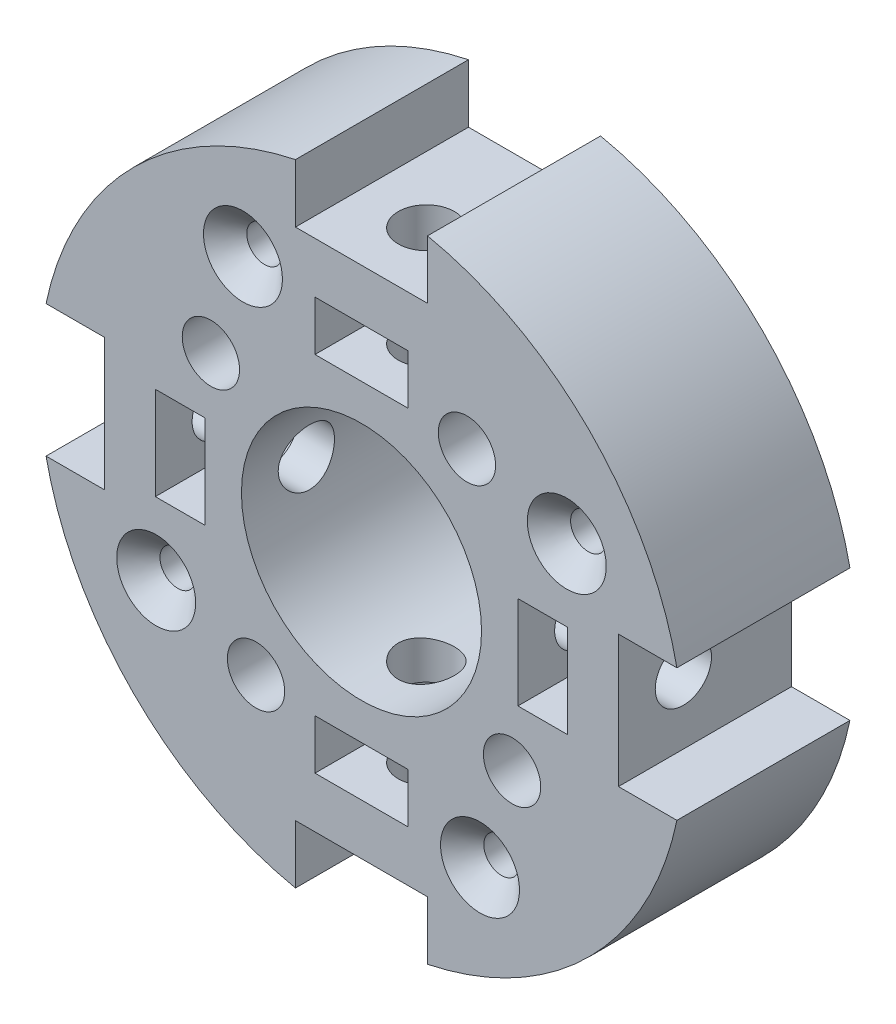
SolidWorks part; units mm, degrees
ref_plane "Plan de face" through (0, 0, 0) normal (0, 0, 1) x (1, 0, 0)
ref_plane "Plan de dessus" through (0, 0, 0) normal (0, 1, 0) x (1, 0, 0)
ref_plane "Plan de droite" through (0, 0, 0) normal (1, 0, 0) x (0, 0, -1)
sketch "Esquisse1" plane through (0, 0, 0) normal (0, 0, 1) x (1, 0, 0)
  line L1 (-29.4129, -5.9059) -> (-23.9629, -5.9059) construction
  line L3 (-29.4129, 5.9059) -> (-23.9629, 5.9059) construction
  line L4 (-23.9629, -5.9059) -> (-23.9629, 5.9059) construction
  line L5 (-29.4129, -5.9059) -> (-23.9629, 5.9059) construction
  line L6 (-29.4129, 5.9059) -> (-23.9629, -5.9059) construction
  line L7 (-5.9059, 29.4129) -> (-5.9059, 23.9629) construction
  line L8 (-5.9059, 23.9629) -> (5.9059, 23.9629) construction
  line L9 (5.9059, 29.4129) -> (5.9059, 23.9629) construction
  line L11 (29.4129, 5.9059) -> (23.9629, 5.9059) construction
  line L12 (23.9629, 5.9059) -> (23.9629, -5.9059) construction
  line L13 (29.4129, -5.9059) -> (23.9629, -5.9059) construction
  line L15 (5.9059, -29.4129) -> (5.9059, -23.9629) construction
  line L16 (5.9059, -23.9629) -> (-5.9059, -23.9629) construction
  line L17 (-5.9059, -29.4129) -> (-5.9059, -23.9629) construction
  line L18 (-6.1059, 29.1677) -> (-6.1059, 23.7629)
  line L19 (-6.1059, 23.7629) -> (6.1059, 23.7629)
  line L20 (6.1059, 29.1677) -> (6.1059, 23.7629)
  line L21 (29.1677, 6.1059) -> (23.7629, 6.1059)
  line L22 (23.7629, 6.1059) -> (23.7629, -6.1059)
  line L23 (29.1677, -6.1059) -> (23.7629, -6.1059)
  line L24 (6.1059, -29.1677) -> (6.1059, -23.7629)
  line L25 (6.1059, -23.7629) -> (-6.1059, -23.7629)
  line L26 (-6.1059, -29.1677) -> (-6.1059, -23.7629)
  line L27 (-29.1677, -6.1059) -> (-23.7629, -6.1059)
  line L28 (-23.7629, -6.1059) -> (-23.7629, 6.1059)
  line L29 (-29.1677, 6.1059) -> (-23.7629, 6.1059)
  line L30 (-4.3, 19.0629) -> (4.3, 19.0629)
  line L31 (-4, 18.7629) -> (4, 18.7629) construction
  line L32 (-4, 18.7629) -> (-4, 14.7629) construction
  line L33 (-4, 14.7629) -> (4, 14.7629) construction
  line L34 (4, 18.7629) -> (4, 14.7629) construction
  line L35 (-4, 18.7629) -> (4, 14.7629) construction
  line L36 (-4, 14.7629) -> (4, 18.7629) construction
  line L37 (4.3, 19.0629) -> (4.3, 14.4629)
  line L38 (-4.3, 14.4629) -> (4.3, 14.4629)
  line L39 (-4.3, 19.0629) -> (-4.3, 14.4629)
  line L40 (19.0629, 4.3) -> (19.0629, -4.3)
  line L41 (19.0629, -4.3) -> (14.4629, -4.3)
  line L42 (14.4629, 4.3) -> (14.4629, -4.3)
  line L43 (19.0629, 4.3) -> (14.4629, 4.3)
  line L44 (4.3, -19.0629) -> (-4.3, -19.0629)
  line L45 (-4.3, -19.0629) -> (-4.3, -14.4629)
  line L46 (4.3, -14.4629) -> (-4.3, -14.4629)
  line L47 (4.3, -19.0629) -> (4.3, -14.4629)
  line L48 (-19.0629, -4.3) -> (-19.0629, 4.3)
  line L49 (-19.0629, 4.3) -> (-14.4629, 4.3)
  line L50 (-14.4629, -4.3) -> (-14.4629, 4.3)
  line L51 (-19.0629, -4.3) -> (-14.4629, -4.3)
  line L52 (-0.2119, 0.3671) -> (-25000.2119, 43301.6373) construction
  line L53 (0, 0) -> (-40957.6022, 28678.8218) construction
  line L54 (0, -1000) -> (0, 49000) construction
  arc A0 (-29.4129, -5.9059) -> (-5.9059, -29.4129) centre (0, 0) ccw construction
  circle A1 centre (0, 0) radius 11.1
  circle A2 centre (-10.9602, 18.9835) radius 1.65
  circle A3 centre (18.9835, 10.9602) radius 1.65
  circle A4 centre (10.9602, -18.9835) radius 1.65
  circle A5 centre (-18.9835, -10.9602) radius 1.65
  arc A6 (5.9059, -29.4129) -> (29.4129, -5.9059) centre (0, 0) ccw construction
  arc A7 (29.4129, 5.9059) -> (5.9059, 29.4129) centre (0, 0) ccw construction
  arc A8 (-5.9059, 29.4129) -> (-29.4129, 5.9059) centre (0, 0) ccw construction
  arc A9 (29.1677, 6.1059) -> (6.1059, 29.1677) centre (0, 0) ccw
  arc A10 (6.1059, -29.1677) -> (29.1677, -6.1059) centre (0, 0) ccw
  arc A11 (-29.1677, -6.1059) -> (-6.1059, -29.1677) centre (0, 0) ccw
  arc A12 (-6.1059, 29.1677) -> (-29.1677, 6.1059) centre (0, 0) ccw
  circle A13 centre (-13.9256, 9.7508) radius 2.65
  circle A14 centre (9.7508, 13.9256) radius 2.65
  circle A15 centre (13.9256, -9.7508) radius 2.65
  circle A16 centre (-9.7508, -13.9256) radius 2.65
  point P4 (-26.6879, 0)
  point P22 (0, 0)
  point P33 (0, 0)
  point P51 (0, 16.7629)
  point P56 (0, 23.7629)
  point P75 (0, 0)
  point P90 (0, 0)
  dimension "D1" = 60
  dimension "D2" = 22.2
  dimension "D7" = 3.3
  dimension "D14" = 5.3
  dimension "D18" = 4
  dimension "D3" = 5.45
  dimension "D4" = 4
  dimension "D5" = 21.9203
  dimension "D6" = 0.2
  dimension "D9" = 8
  dimension "D10" = 4
  dimension "D11" = 5
  dimension "D15" = 17
  dimension "D16" = 30
  dimension "D17" = 55
  dimension "D12" = 0.3
  dimension "D8" = 4
  dimension "D13" = 4
extrude "Boss.-Extru.1" add sketch "Esquisse1" along normal blind 16 contours A0 A1 A2 A3 | A0 A1 A5 A4 | A0 | A0 region at (-6.9309, 26.4653, 0)
sketch "Esquisse5" plane through (0, 0, 0) normal (0, 0, -1) x (-1, 0, 0)
  line L0 (9.1913, 9.7508) -> (11.5584, 5.6508)
  line L1 (-9.7508, 9.1913) -> (-5.6508, 11.5584)
  line L2 (-5.6508, 11.5584) -> (-5.6508, 16.2927)
  line L3 (-5.6508, 16.2927) -> (-9.7508, 18.6599)
  line L4 (-9.7508, 18.6599) -> (-13.8508, 16.2927)
  line L5 (-13.8508, 16.2927) -> (-13.8508, 11.5584)
  line L6 (-13.8508, 11.5584) -> (-9.7508, 9.1913)
  line L7 (11.5584, 5.6508) -> (16.2927, 5.6508)
  line L8 (16.2927, 5.6508) -> (18.6599, 9.7508)
  line L9 (18.6599, 9.7508) -> (16.2927, 13.8508)
  line L10 (16.2927, 13.8508) -> (11.5584, 13.8508)
  line L11 (11.5584, 13.8508) -> (9.1913, 9.7508)
  line L12 (9.7508, -9.1913) -> (5.6508, -11.5584)
  line L13 (5.6508, -11.5584) -> (5.6508, -16.2927)
  line L14 (5.6508, -16.2927) -> (9.7508, -18.6599)
  line L15 (9.7508, -18.6599) -> (13.8508, -16.2927)
  line L16 (13.8508, -16.2927) -> (13.8508, -11.5584)
  line L17 (13.8508, -11.5584) -> (9.7508, -9.1913)
  line L18 (-9.1913, -9.7508) -> (-11.5584, -5.6508)
  line L19 (-11.5584, -5.6508) -> (-16.2927, -5.6508)
  line L20 (-16.2927, -5.6508) -> (-18.6599, -9.7508)
  line L21 (-18.6599, -9.7508) -> (-16.2927, -13.8508)
  line L22 (-16.2927, -13.8508) -> (-11.5584, -13.8508)
  line L23 (-11.5584, -13.8508) -> (-9.1913, -9.7508)
  circle A0 centre (-9.7508, 13.9256) radius 4.1 construction
  point P30 (0, 0)
  dimension "D1" = 8.2
  dimension "D2" = 4
extrude "Enlèv. mat.-Extru.3" cut sketch "Esquisse5" against normal blind 10
chamfer "Chanfrein1" distance 2 angle 45 4 edges at (-17.3335, -10.9602, 16) (12.6102, -18.9835, 16) (20.6335, 10.9602, 16) (-9.3102, 18.9835, 16)
sketch "Esquisse6" plane through (-23.7629, 0, 0) normal (-1, 0, 0) x (0, 0, 1)
  line L1 (16, -6.1059) -> (16, 6.1059) construction
  circle A0 centre (10, 0) radius 2.6
  dimension "D1" = 5.2
  dimension "D2" = 6
extrude "Enlèv. mat.-Extru.4" cut sketch "Esquisse6" against normal blind 17
pattern_circular "Répétition circulaire1" count 4 every 90 about axis through (0, 0, 0) along (0, 0, 1) of "Enlèv. mat.-Extru.4"
